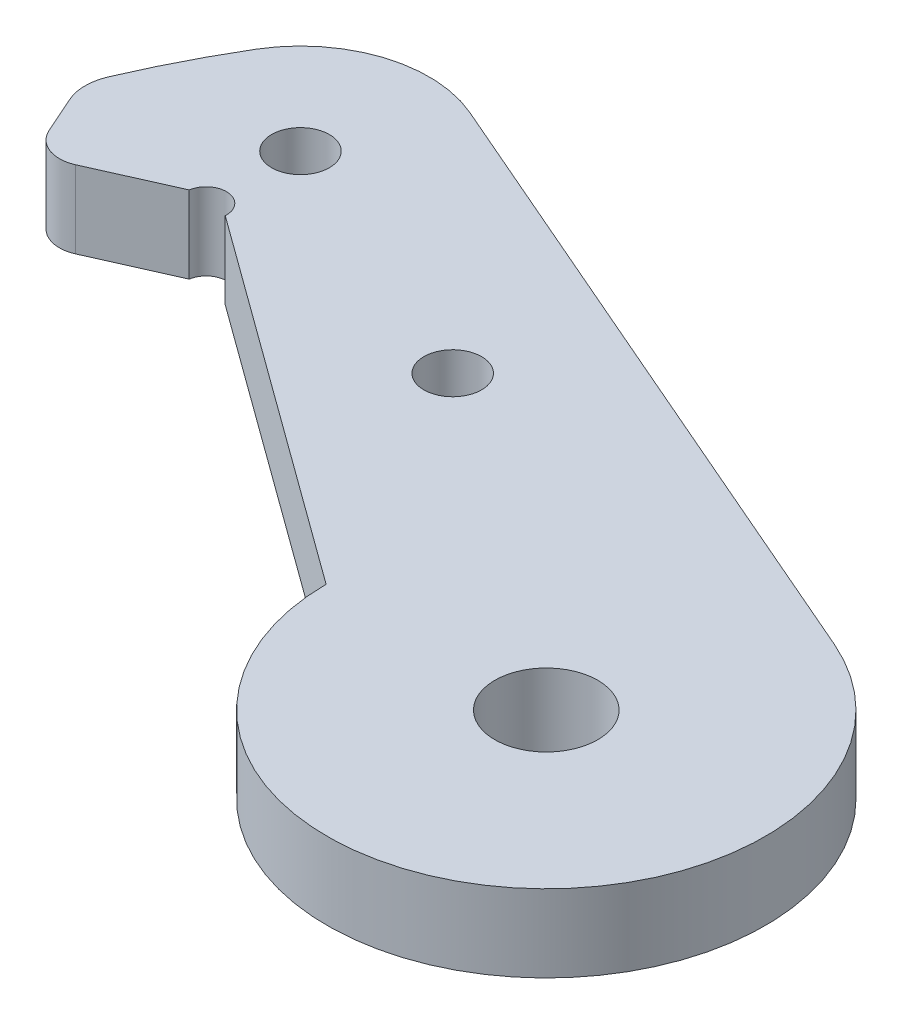
SolidWorks part; units mm, degrees
ref_plane "Front" through (0, 0, 0) normal (0, 0, 1) x (1, 0, 0)
ref_plane "Top" through (0, 0, 0) normal (0, 1, 0) x (1, 0, 0)
ref_plane "Right" through (0, 0, 0) normal (1, 0, 0) x (0, 0, -1)
ref_axis "side-side" through (80.9, 0, 0) along (-1, 0, 0)
ref_axis "up-down" through (0, 50, 0) along (0, -1, 0)
ref_axis "front-back" through (0, 0, -80.9) along (0, 0, 1)
sketch "Sketch1" plane through (0, 0, 0) normal (0, 1, 0) x (1, 0, 0)
  line L0 (-37.5348, 16.5677) -> (-37.4529, 17.3438) construction
  line L1 (-38.7702, 16.758) -> (-43.6254, 14.5987)
  line L2 (-36.2869, 16.4959) -> (-13.4998, -0.0747)
  line L3 (-46.2656, 15.6135) -> (-47.2827, 17.9005)
  line L4 (-34.2596, 29.5434) -> (5.3636, 12.3888) construction
  line L5 (-34.2596, 29.5434) -> (5.3636, 12.3888)
  line L6 (-36.2869, 16.4959) -> (-38.7702, 16.758) construction
  arc A0 (-43.6254, 14.5987) -> (-46.2656, 15.6135) centre (-44.4381, 16.4262) cw
  arc A1 (-47.2983, 20.3029) -> (-44.2347, 26.3178) centre (0, 0) cw
  arc A2 (-47.2983, 20.3029) -> (-47.2827, 17.9005) centre (-44.5415, 19.1196) ccw
  arc A3 (-34.2596, 29.5434) -> (-44.2347, 26.3178) centre (-37.4133, 22.2593) ccw
  arc A4 (-38.7702, 16.758) -> (-36.2869, 16.4959) centre (-37.5348, 16.5677) cw
  arc A5 (-13.4998, -0.0747) -> (5.3636, 12.3888) centre (0, 0) ccw
  circle A10 centre (8, 0) radius 1.75 construction
  circle A11 centre (0, -8) radius 1.75 construction
  circle A12 centre (-8, 0) radius 1.75 construction
  circle A13 centre (0, 8) radius 1.75 construction
  circle A14 centre (-20.8625, 15.0937) radius 1.778
  circle A15 centre (0, 0) radius 3.175
  circle A16 centre (-20.8625, 15.0937) radius 7.9375 construction
  arc A17 (-34.2596, 29.5434) -> (-44.2347, 26.3178) centre (-37.4133, 22.2593) ccw construction
  circle A18 centre (-37.4133, 22.2593) radius 1.778
  point P0 (-37.4529, 17.3438)
  point P11 (-45.4529, 13.786)
  dimension "D2" = 3
  dimension "D8" = 2
  dimension "D9" = 0.7804
  dimension "D7" = 1.25
  dimension "D11" = 15.875
  dimension "D13" = 6.35
  dimension "D14" = 3.556
  dimension "D1" = 8.7554
  dimension "D3" = 8
  dimension "D6" = 120
  dimension "D12" = 25.75
extrude "Boss-Extrude1" add sketch "Sketch1" along normal blind 4.7625
